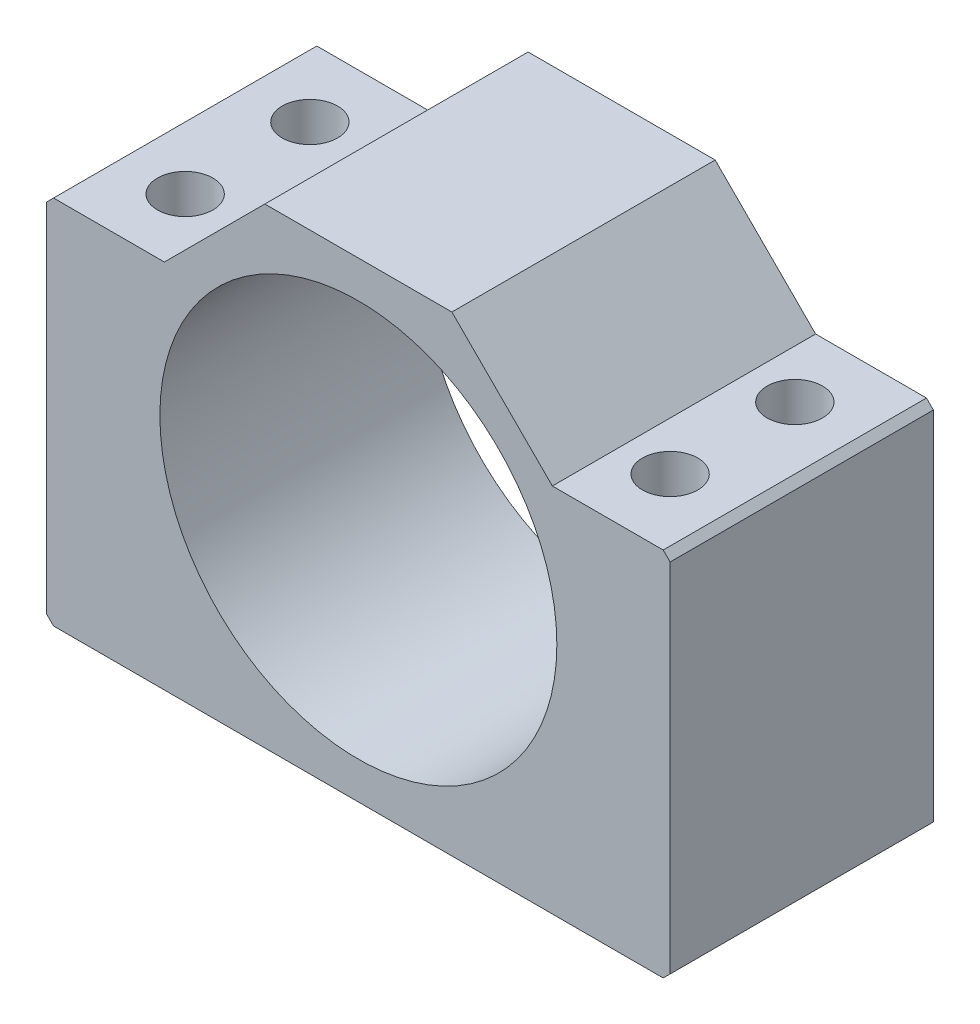
SolidWorks part; units mm, degrees
ref_plane "Front Plane" through (0, 0, 0) normal (0, 0, 1) x (1, 0, 0)
ref_plane "Top Plane" through (0, 0, 0) normal (0, 1, 0) x (1, 0, 0)
ref_plane "Right Plane" through (0, 0, 0) normal (1, 0, 0) x (0, 0, -1)
sketch "Sketch1" plane through (0, 0, 0) normal (0, 0, 1) x (1, 0, 0)
  line L1 (-45, -34) -> (45, -34)
  line L2 (-45, -34) -> (-45, 34)
  line L3 (-45, 34) -> (45, 34)
  line L4 (45, -34) -> (45, 34)
  line L5 (-45, -34) -> (45, 34) construction
  line L6 (-45, 34) -> (45, -34) construction
  circle A0 centre (0, 0) radius 28.65
  point P0 (0, 0)
  dimension "D3" = 57.3
  dimension "D1" = 90
  dimension "D2" = 68
extrude "Boss-Extrude1" add sketch "Sketch1" along normal mid plane 38
sketch "Sketch2" plane through (0, 34, 0) normal (0, 1, 0) x (1, 0, 0)
  line L0 (-35, 19) -> (-35, -19) construction
  line L1 (45, 19) -> (-45, 19) construction
  line L2 (45, -19) -> (-45, -19) construction
  line L3 (35, 19) -> (35, -19) construction
  line L4 (-45, -19) -> (-45, 19) construction
  line L5 (45, -19) -> (45, 19) construction
  line L6 (-45, 9) -> (45, 9) construction
  line L7 (-45, -9) -> (45, -9) construction
  line L8 (-45, 0) -> (45, 0) construction
  line L9 (0, 19) -> (0, -19) construction
  circle A0 centre (-35, 9) radius 4
  circle A1 centre (-35, -9) radius 4
  circle A2 centre (35, 9) radius 4
  circle A3 centre (35, -9) radius 4
  dimension "D5" = 8
  dimension "D6" = 8
  dimension "D7" = 8
  dimension "D8" = 8
  dimension "D1" = 35
  dimension "D2" = 35
  dimension "D3" = 9
  dimension "D4" = 9
extrude "Cut-Extrude1" cut sketch "Sketch2" against normal through all
sketch "Sketch3" plane through (0, 0, 19) normal (0, 0, 1) x (1, 0, 0)
  line L0 (-45, 19.5) -> (-28, 19.5)
  line L1 (-45, 34) -> (-45, -34) construction
  line L2 (-28, 19.5) -> (-13.5, 34)
  line L3 (45, 34) -> (-45, 34) construction
  line L4 (-13.5, 34) -> (-45, 34)
  line L5 (-45, 34) -> (-45, 19.5)
  line L6 (-45, -34) -> (45, -34) construction
  line L7 (45, 19.5) -> (28, 19.5)
  line L8 (45, -34) -> (45, 34) construction
  line L9 (28, 19.5) -> (13.5, 34)
  line L10 (13.5, 34) -> (45, 34)
  line L11 (45, 34) -> (45, 19.5)
  dimension "D1" = 53.5
  dimension "D2" = 13.5
  dimension "D3" = 135
  dimension "D4" = 135
  dimension "D5" = 13.5
extrude "Cut-Extrude2" cut sketch "Sketch3" against normal through all
chamfer "Chamfer1" distance 1 angle 45 4 edges at (-45, 19.5, 0) (45, 19.5, 0) (45, -34, 0) (-45, -34, 0)
equation "\"D6@Sketch2\"=\"D5@Sketch2\""
equation "\"D7@Sketch2\"=\"D5@Sketch2\""
equation "\"D8@Sketch2\"=\"D5@Sketch2\""
equation "\"D2@Sketch3\"=27/2"
equation "\"D5@Sketch3\"=\"D2@Sketch3\""
